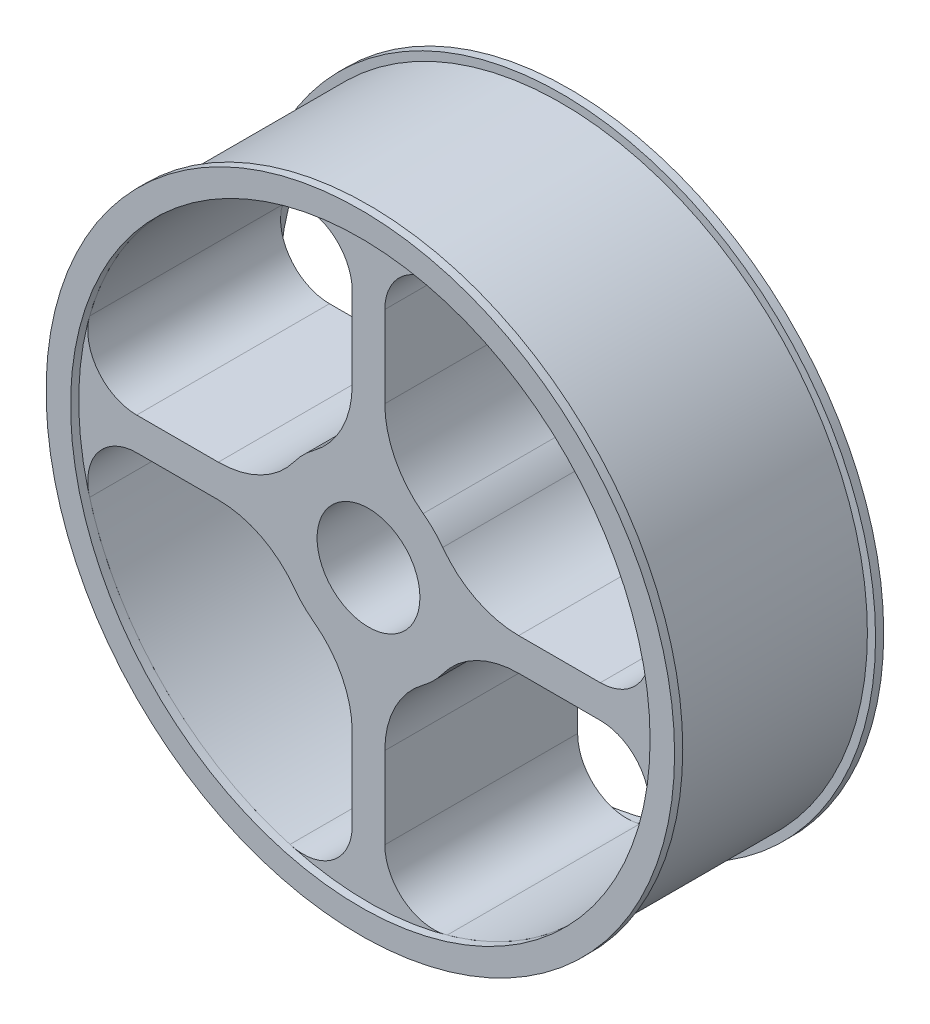
SolidWorks part; units mm, degrees
material "ABS"
ref_plane "Front Plane" through (0, 0, 0) normal (0, 0, 1) x (1, 0, 0)
ref_plane "Top Plane" through (0, 0, 0) normal (0, 1, 0) x (1, 0, 0)
ref_plane "Right Plane" through (0, 0, 0) normal (1, 0, 0) x (0, 0, -1)
sketch "Sketch1" plane through (0, 0, 0) normal (0, 0, 1) x (1, 0, 0)
  line L0 (0, 2.87) -> (0, 9.017) construction
  line L2 (0.508, 7.2135) -> (0.508, 4.6735)
  line L4 (-0.508, 7.2135) -> (-0.508, 4.6735)
  line L5 (7.2135, 0.508) -> (4.6735, 0.508)
  line L6 (0, 5.9435) -> (-0.508, 5.9435) construction
  line L7 (7.2135, -0.508) -> (4.6735, -0.508)
  line L8 (0.508, -7.2135) -> (0.508, -4.6735)
  line L9 (-0.508, -7.2135) -> (-0.508, -4.6735)
  line L10 (-7.2135, -0.508) -> (-4.6735, -0.508)
  line L11 (-7.2135, 0.508) -> (-4.6735, 0.508)
  circle A1 centre (0, 0) radius 2.87
  circle A5 centre (0, 0) radius 9.017
  circle A7 centre (0, 0) radius 9.525
  circle A8 centre (0, 0) radius 9.779
  arc A9 (-0.508, 7.2135) -> (-2.4438, 8.6795) centre (-2.031, 7.2135) ccw
  arc A10 (-0.508, 4.6735) -> (-1.7021, 2.3108) centre (-3.4425, 4.6735) cw
  arc A11 (0.508, 4.6735) -> (1.7021, 2.3108) centre (3.4425, 4.6735) ccw
  arc A12 (0.508, 7.2135) -> (2.4438, 8.6795) centre (2.031, 7.2135) cw
  arc A13 (4.6735, 0.508) -> (2.3108, 1.7021) centre (4.6735, 3.4425) cw
  arc A14 (7.2135, 0.508) -> (8.6795, 2.4438) centre (7.2135, 2.031) ccw
  arc A15 (7.2135, -0.508) -> (8.6795, -2.4438) centre (7.2135, -2.031) cw
  arc A16 (4.6735, -0.508) -> (2.3108, -1.7021) centre (4.6735, -3.4425) ccw
  arc A17 (0.508, -4.6735) -> (1.7021, -2.3108) centre (3.4425, -4.6735) cw
  arc A18 (0.508, -7.2135) -> (2.4438, -8.6795) centre (2.031, -7.2135) ccw
  arc A19 (-0.508, -7.2135) -> (-2.4438, -8.6795) centre (-2.031, -7.2135) cw
  arc A20 (-0.508, -4.6735) -> (-1.7021, -2.3108) centre (-3.4425, -4.6735) ccw
  arc A21 (-4.6735, -0.508) -> (-2.3108, -1.7021) centre (-4.6735, -3.4425) cw
  arc A22 (-7.2135, -0.508) -> (-8.6795, -2.4438) centre (-7.2135, -2.031) ccw
  arc A23 (-7.2135, 0.508) -> (-8.6795, 2.4438) centre (-7.2135, 2.031) cw
  arc A24 (-4.6735, 0.508) -> (-2.3108, 1.7021) centre (-4.6735, 3.4425) ccw
  circle A25 centre (0, 0) radius 1.6
  circle A26 centre (0, 0) radius 1.6 construction
  point P64 (0, 0)
  dimension "D1" = 1.27
  dimension "D2" = 0.508
  dimension "D3" = 19.05
  dimension "D4" = 0.254
  dimension "D5" = 0.508
  dimension "D6" = 2.54
  dimension "D7" = 4
extrude "Boss-Extrude1" add sketch "Sketch1" along normal mid plane 6 contours A7 A5 | L2 A12 A5 A9 L4 A10 A1 A11 | A16 L7 A15 A5 A14 L5 A13 A1 | A24 L11 A23 A5 A22 L10 A21 A1 | A20 L9 A19 A5 A18 L8 A17 A1 | A1 A25 region at (0, 6.0984, 0) region at (1.972, 1.972, 0) region at (6.0984, 0, 0) region at (-6.0984, 0, 0) region at (0, -6.0984, 0) region at (-9.2556, 0, 0)
extrude "Boss-Extrude2" add sketch "Sketch1<5>" along normal blind 0.254 from surface separate body contours A7 A5 | A8 A7 region at (-9.2556, 0, 0) region at (-9.7513, 0, 0) starting at face at (3.5712, -3.5712, 3)
sketch "Sketch1<5>" plane through (0, 0, 0) normal (0, 0, 1) x (1, 0, 0) same geometry as "Sketch1"
mirror "Mirror2" about plane through (0, 0, 0) normal (0, 0, 1) of bodies 105 102
